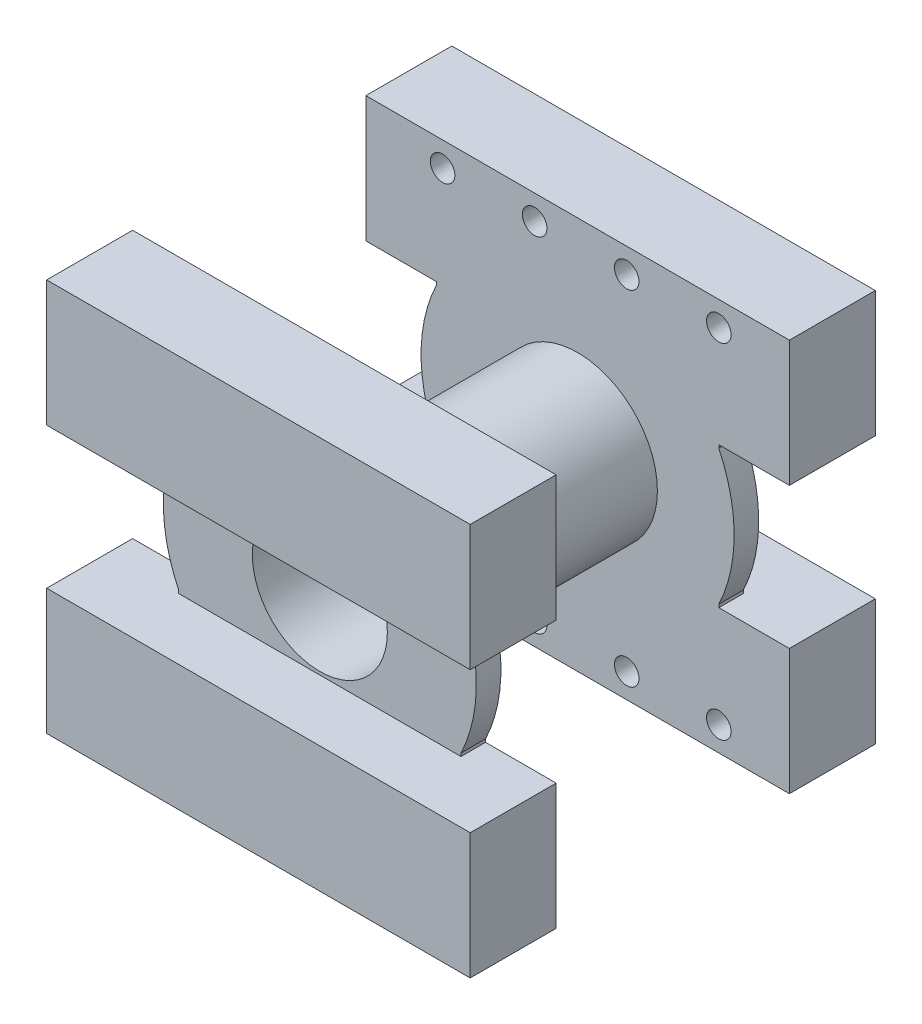
SolidWorks part; units mm, degrees
ref_plane "Front Plane" through (0, 0, 0) normal (0, 0, 1) x (1, 0, 0)
ref_plane "Top Plane" through (0, 0, 0) normal (0, 1, 0) x (1, 0, 0)
ref_plane "Right Plane" through (0, 0, 0) normal (1, 0, 0) x (0, 0, -1)
sketch "Sketch1" plane through (0, 0, 0) normal (0, 0, 1) x (1, 0, 0)
  line L0 (11.5, 5.5057) -> (11.5, 16)
  line L1 (11.5, -16) -> (-11.5, -16)
  line L2 (11.5, -16) -> (11.5, -5.5057)
  line L3 (11.5, 16) -> (-11.5, 16)
  line L4 (-11.5, -16) -> (-11.5, -5.5057)
  line L5 (11.5, -16) -> (-11.5, 16) construction
  line L6 (11.5, 16) -> (-11.5, -16) construction
  line L7 (-11.5, 5.5057) -> (-11.5, 16)
  circle A0 centre (0, 0) radius 5.5
  arc A1 (-11.5, 5.5057) -> (-11.5, -5.5057) centre (0, 0) ccw
  arc A2 (11.5, -5.5057) -> (11.5, 5.5057) centre (0, 0) ccw
  circle A3 centre (0, 0) radius 6.5
  dimension "D1" = 11
  dimension "D2" = 25.5
  dimension "D5" = 13
  dimension "D3" = 23
  dimension "D4" = 32
extrude "Boss-Extrude1" add sketch "Sketch1" along normal mid plane 2 contours L2 A2 L0 L3 L7 A1 L4 L1 A3 | A3 A0 region at (12.3408, 0, 0) region at (-6.3162, 0, 0)
sketch "Sketch2" plane through (0, 0, 1) normal (0, 0, 1) x (1, 0, 0)
  circle A1 centre (0, 0) radius 6.5
  circle A2 centre (0, 0) radius 5.5
  dimension "D1" = 13
  dimension "D2" = 11
sketch "Sketch3" plane through (0, 0, -1) normal (0, 0, -1) x (-1, 0, 0)
  line L3 (17.25, 5.75) -> (-17.25, 5.75)
  line L5 (-15.6987, 0) -> (19.4146, 0) construction
  line L6 (17.25, -16) -> (17.25, -5.75)
  line L7 (-17.25, 5.75) -> (-17.25, 16)
  line L8 (-17.25, 16) -> (17.25, 16)
  line L9 (17.25, 16) -> (17.25, 5.75)
  line L10 (-17.25, -16) -> (17.25, -16)
  line L11 (-17.25, -5.75) -> (-17.25, -16)
  line L12 (17.25, -5.75) -> (-17.25, -5.75)
  point P0 (0, 0)
  point P7 (0, 5.75)
  dimension "D1" = 11.5
  dimension "D2" = 34.5
extrude "Boss-Extrude4" add sketch "Sketch2" along normal blind 19
extrude "Boss-Extrude5" add sketch "Sketch3" along normal blind 5 and the other way up to surface (2 mm away) other way up to face at (0, 0, 1)
ref_plane "Plane1" through (0, 0, 10.5) normal (0, 0, 1) x (1, 0, 0)
mirror "Mirror1" about plane through (0, 0, 10.5) normal (0, 0, 1) of "Boss-Extrude5", "Boss-Extrude1"
sketch "Sketch4" plane through (0, 0, -6) normal (0, 0, -1) x (-1, 0, 0)
  line L0 (-17.6861, 0) -> (22.8967, 0) construction
  line L1 (-16.2832, 14) -> (14.9805, 14) construction
  line L2 (0, 20.0666) -> (0, -21.7538) construction
  line L3 (-17.25, 16) -> (-17.25, 5.75) construction
  circle A0 centre (-11.5, 14) radius 1
  circle A8 centre (-4, 14) radius 1
  circle A9 centre (3.5, 14) radius 1
  circle A10 centre (11, 14) radius 1
  circle A11 centre (11, -14) radius 1
  circle A12 centre (3.5, -14) radius 1
  circle A13 centre (-4, -14) radius 1
  circle A14 centre (-11.5, -14) radius 1
  point P17 (11.5, -14)
  dimension "D4" = 2
  dimension "D1" = 14
  dimension "D2" = 4
  dimension "D3" = 5.75
extrude "Cut-Extrude1" cut sketch "Sketch4" against normal blind 10
